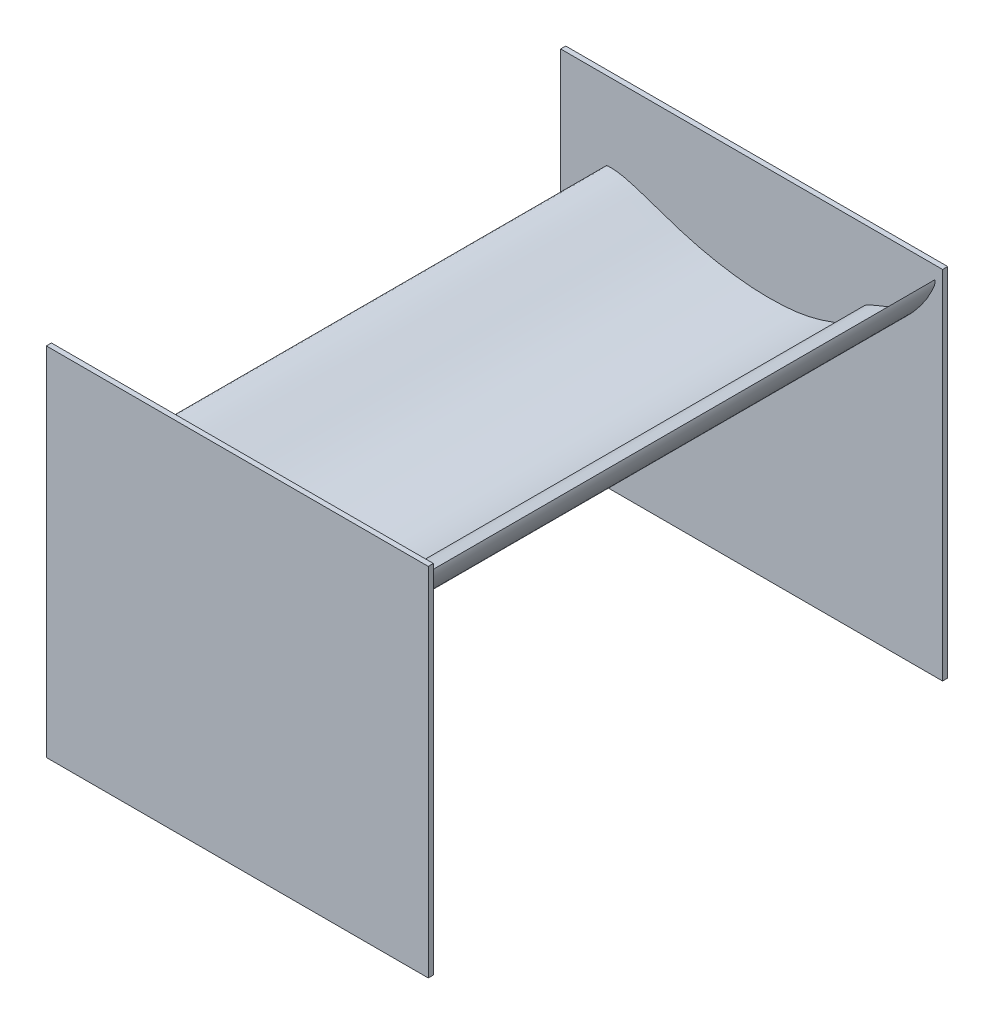
SolidWorks part; units mm, degrees
ref_plane "Front Plane" through (0, 0, 0) normal (0, 0, 1) x (1, 0, 0)
ref_plane "Top Plane" through (0, 0, 0) normal (0, 1, 0) x (1, 0, 0)
ref_plane "Right Plane" through (0, 0, 0) normal (1, 0, 0) x (0, 0, -1)
sketch "Sketch8" plane through (0, 0, 0) normal (0, 0, 1) x (1, 0, 0)
  line L0 (0, 500) -> (923, 500) construction
  line L1 (0, 0) -> (923, 0) construction
  line L2 (0, 0) -> (0, 1200) construction
  line L3 (0, 1200) -> (923, 1200) construction
  line L4 (923, 0) -> (923, 1200) construction
  line L5 (-114, 1134) -> (686, 312.7) construction
  line L6 (273.2997, 1047.4592) -> (2273.2997, 1047.4592) construction
  line L7 (273.2997, 1047.4592) -> (773.2236, 1038.733) construction
  line L8 (770.1981, 1062.2592) -> (908.1, 1170) construction
  line L9 (260.1585, 1071.9162) -> (260.1585, 873.8931) construction
  line L14 (173, 1200) -> (923, 1200)
  line L15 (173, 1200) -> (173, 500)
  line L16 (173, 500) -> (923, 500)
  line L17 (923, 1200) -> (923, 500)
  line L18 (767.5582, 1104.7796) -> (767.5582, 1035.6822) construction
  circle A0 centre (-238, 828) radius 150 construction
  spline S0 degree 3 poles (772.0752, 1063.6972) (770.255, 1062.3396) (769.0137, 1061.2545) (768.2597, 1060.4953) (767.9209, 1060.1383) (767.7558, 1059.9199) (767.6734, 1059.7831) (767.616, 1059.654) (767.5789, 1059.5287) (767.5582, 1059.3879) (767.5563, 1059.2073) (767.5893, 1058.9358) (767.6578, 1058.6654) (767.7751, 1058.2938) (767.9453, 1057.8834) (768.2368, 1057.378) (768.5583, 1056.9513) (769.0298, 1056.431) (769.806, 1055.7407) (770.8808, 1055.0065) (772.1983, 1054.1926) (773.6293, 1053.425) (775.358, 1052.7286) (777.23, 1052.1573) (779.3102, 1051.6977) (781.6009, 1051.3645) (784.0892, 1051.1848) (786.747, 1051.1714) (789.5825, 1051.3327) (792.6212, 1051.6757) (795.3452, 1052.1278) (798.2182, 1052.7282) (801.1813, 1053.478) (804.6933, 1054.5601) (808.2564, 1055.8541) (811.8688, 1057.3653) (815.5197, 1059.0959) (818.1188, 1060.4717) (820.8916, 1062.0156) (823.8637, 1063.7628) (828.2331, 1066.5218) (832.8984, 1069.6437) (837.6895, 1073.0835) (842.3159, 1076.6611) (846.6972, 1080.3135) (850.9488, 1084.1079) (855.2182, 1088.1728) (859.4984, 1092.5133) (863.8007, 1097.1473) (868.0963, 1102.0452) (872.4459, 1107.2817) (876.8688, 1112.8911) (881.1551, 1118.5931) (885.1567, 1124.2014) (888.8717, 1129.7109) (892.368, 1135.242) (895.6768, 1140.8716) (898.7255, 1146.4549) (901.4035, 1151.7628) (903.6462, 1156.5411) (905.2967, 1160.395) (906.4624, 1163.3861) (907.2456, 1165.6787) (907.7631, 1167.6439) (908.0862, 1169.5112) (908.204, 1171.4861) (908.1593, 1173.0213) (907.8622, 1176.1901) (907.7026, 1171.8491) (907.2069, 1169.8738) (906.5505, 1167.0951) (905.6846, 1164.542) (904.6107, 1161.8703) (903.1889, 1158.8278) (900.9781, 1154.6405) (898.3664, 1149.9942) (895.6142, 1145.2708) (893.122, 1141.3619) (890.5205, 1137.6008) (887.7704, 1133.9697) (884.8317, 1130.4246) (881.7649, 1127.0384) (878.4915, 1123.7156) (874.8834, 1120.2925) (870.8177, 1116.6427) (866.3625, 1112.8916) (861.6946, 1109.2259) (856.7805, 1105.6379) (851.6225, 1102.1321) (846.1521, 1098.658) (840.4388, 1095.2399) (834.5249, 1091.9151) (828.5376, 1088.7888) (822.5993, 1085.9281) (816.4886, 1083.1874) (809.895, 1080.4148) (802.6134, 1077.5316) (795.3838, 1074.7749) (789.0061, 1072.2398) (784.0517, 1070.1195) (780.1508, 1068.3145) (776.9683, 1066.6835) (774.2902, 1065.1443) (772.0752, 1063.6972) (770.255, 1062.3396) (769.0137, 1061.2545) knots -0.020104 -0.012389 -0.005583 0 0.004865 0.006933 0.008138 0.008601 0.009012 0.009349 0.009673 0.010003 0.010428 0.011042 0.012077 0.012543 0.014005 0.015444 0.016969 0.018056 0.02078 0.024841 0.027936 0.032555 0.037166 0.042082 0.047422 0.053348 0.059667 0.066375 0.073542 0.081249 0.089615 0.094526 0.103562 0.112844 0.122456 0.132374 0.142605 0.153166 0.154726 0.166736 0.179372 0.194013 0.209411 0.224207 0.23847 0.252772 0.267526 0.283284 0.299114 0.315597 0.332811 0.350866 0.369905 0.387044 0.403244 0.420423 0.436787 0.452885 0.468783 0.481983 0.493012 0.500655 0.506382 0.511438 0.516044 0.520926 0.525831 0.529954 0.53661 0.543291 0.550106 0.557027 0.564113 0.571894 0.58258 0.600094 0.612425 0.624138 0.635332 0.647187 0.658759 0.670333 0.681913 0.694215 0.708142 0.723449 0.738488 0.75326 0.769704 0.785898 0.802526 0.820319 0.837475 0.853872 0.870428 0.888391 0.908253 0.929971 0.947221 0.960431 0.970941 0.979896 0.987611 0.994417 1 1.004865 1.006933 1.008138 only from (770.1981, 1062.2592) to (770.1981, 1062.2592)
  spline S1 degree 3 poles (279.936, 1047.1295) (273.5678, 1047.5282) (268.9353, 1047.4586) (265.9395, 1047.2021) (264.5646, 1047.0527) (263.8137, 1046.8847) (263.3886, 1046.7414) (263.0309, 1046.5691) (262.7236, 1046.3678) (262.4233, 1046.1036) (262.0912, 1045.7202) (261.6684, 1045.0784) (261.3236, 1044.3743) (260.8998, 1043.3648) (260.5184, 1042.1758) (260.2247, 1040.5628) (260.1381, 1039.0643) (260.2031, 1037.0921) (260.6119, 1034.2021) (261.5807, 1030.6751) (262.9249, 1026.5363) (264.5967, 1022.2904) (267.0356, 1017.6559) (270.0095, 1013.0292) (273.632, 1008.2636) (277.9358, 1003.3859) (282.9417, 998.4783) (288.6133, 993.6191) (294.9832, 988.8113) (302.1189, 984.0233) (308.7784, 980.0413) (316.0267, 976.1064) (323.7399, 972.3278) (333.2329, 968.2637) (343.221, 964.561) (353.7093, 961.234) (364.6791, 958.3073) (372.7497, 956.5319) (381.4984, 954.801) (391.0434, 953.1436) (405.422, 951.1149) (421.0942, 949.3262) (437.6138, 947.9903) (454.0311, 947.2489) (470.059, 947.1132) (486.0667, 947.5177) (502.6046, 948.4694) (519.6665, 949.9924) (537.3092, 952.104) (555.4171, 954.7935) (574.2561, 958.1101) (593.93, 962.0929) (613.4795, 966.5227) (632.2486, 971.2689) (650.2238, 976.3242) (667.7695, 981.8232) (685.0924, 987.8743) (701.7738, 994.2988) (717.1602, 1000.807) (730.6513, 1006.9712) (741.1928, 1012.2307) (749.1275, 1016.5222) (754.9726, 1020.0121) (759.6535, 1023.2831) (763.7399, 1026.6978) (767.5816, 1030.716) (770.2762, 1034.0872) (775.3987, 1041.4184) (767.1669, 1032.4052) (762.5144, 1029.0731) (756.0573, 1024.3109) (749.5614, 1020.4132) (742.4041, 1016.6392) (733.8272, 1012.7031) (721.4788, 1007.7474) (707.4368, 1002.5365) (692.9539, 997.416) (680.5082, 993.5686) (668.0971, 990.2364) (655.6039, 987.4528) (642.8627, 985.1964) (630.1358, 983.5134) (617.0813, 982.3417) (603.1273, 981.5636) (587.7802, 981.1311) (571.4148, 981.1896) (554.7486, 981.8174) (537.6958, 983.0595) (520.2699, 984.9209) (502.232, 987.418) (483.7756, 990.4768) (465.0585, 994.0998) (446.5449, 998.2819) (428.6191, 1002.9441) (410.542, 1008.1768) (391.372, 1014.2188) (370.5267, 1021.2744) (350.0226, 1028.5063) (331.7471, 1034.6648) (317.2755, 1039.1255) (305.6347, 1042.3472) (295.8501, 1044.6359) (287.313, 1046.2047) (279.936, 1047.1295) (273.5678, 1047.5282) (268.9353, 1047.4586) knots -0.020104 -0.012389 -0.005583 0 0.004865 0.006933 0.008138 0.008601 0.009012 0.009349 0.009673 0.010003 0.010428 0.011042 0.012077 0.012543 0.014005 0.015444 0.016969 0.018056 0.02078 0.024841 0.027936 0.032555 0.037166 0.042082 0.047422 0.053348 0.059667 0.066375 0.073542 0.081249 0.089615 0.094526 0.103562 0.112844 0.122456 0.132374 0.142605 0.153166 0.154726 0.166736 0.179372 0.194013 0.209411 0.224207 0.23847 0.252772 0.267526 0.283284 0.299114 0.315597 0.332811 0.350866 0.369905 0.387044 0.403244 0.420423 0.436787 0.452885 0.468783 0.481983 0.493012 0.500655 0.506382 0.511438 0.516044 0.520926 0.525831 0.529954 0.53661 0.543291 0.550106 0.557027 0.564113 0.571894 0.58258 0.600094 0.612425 0.624138 0.635332 0.647187 0.658759 0.670333 0.681913 0.694215 0.708142 0.723449 0.738488 0.75326 0.769704 0.785898 0.802526 0.820319 0.837475 0.853872 0.870428 0.888391 0.908253 0.929971 0.947221 0.960431 0.970941 0.979896 0.987611 0.994417 1 1.004865 1.006933 1.008138 only from (273.2997, 1047.4592) to (273.2997, 1047.4592)
  point P4 (-114, 1134)
  point P8 (0, 828)
  point P9 (686, 312.7)
  point P11 (773.2236, 1038.733)
  point P22 (908.1, 1170)
  dimension "D9" = 300
  dimension "D1" = 1200
  dimension "D2" = 923
  dimension "D3" = 500
  dimension "D4" = 828
  dimension "D5" = 114
  dimension "D6" = 306
  dimension "D7" = 821.3
  dimension "D8" = 800
  dimension "D10" = 238
  dimension "D11" = 500
  dimension "D12" = 175
  dimension "D13" = 662.8415
  dimension "D14" = 14.8
  dimension "D15" = 1
  dimension "D16" = 38
  dimension "D17" = 2000
  dimension "D18" = 30
  dimension "D19" = 14.9
  dimension "D20" = 750
  dimension "D21" = 700
extrude "Boss-Extrude4" add sketch "Sketch8" along normal blind 1000 contours S1 | S0
extrude "Boss-Extrude6" add sketch "Sketch8<4>" against normal blind 10 contours S1 | L17 L14 L15 L16 S1 S0 | S0 region at (552.766, 835.9471, 0) region at (748.8848, 1017.0463, 0)
sketch "Sketch8<4>" plane through (0, 0, 0) normal (0, 0, 1) x (1, 0, 0) same geometry as "Sketch8"
ref_plane "Plane1" through (0, 0, 500) normal (0, 0, 1) x (1, 0, 0)
mirror "Mirror1" about plane through (0, 0, 500) normal (0, 0, 1) of "Boss-Extrude6"
